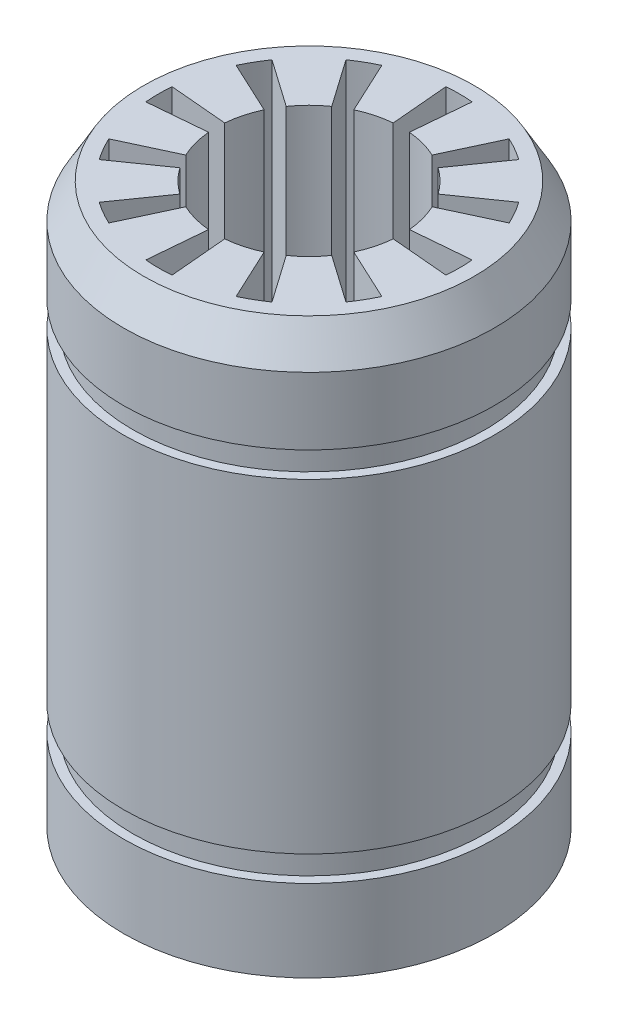
SolidWorks part; units mm, degrees
ref_plane "Front Plane" through (0, 0, 0) normal (0, 0, 1) x (1, 0, 0)
ref_plane "Top Plane" through (0, 0, 0) normal (0, 1, 0) x (1, 0, 0)
ref_plane "Right Plane" through (0, 0, 0) normal (1, 0, 0) x (0, 0, -1)
ref_plane "Plane4" through (0, 0, 0) normal (0, 0, -1) x (-1, 0, 0)
sketch "Sketch1" plane through (0, 0, 0) normal (0, 0, -1) x (-1, 0, 0)
  line L0 (-8, -12.5) -> (0, -12.5)
  line L1 (0, -12.5) -> (0, 12.5)
  line L2 (0, 12.5) -> (-8, 12.5)
  line L3 (-8, 12.5) -> (-8, 8.1)
  line L4 (-8, 8.1) -> (-7.6, 8.1)
  line L5 (-7.6, 8.1) -> (-7.6, 7)
  line L6 (-7.6, 7) -> (-8, 7)
  line L7 (-8, 7) -> (-8, -7)
  line L8 (-8, -7) -> (-7.6, -7)
  line L9 (-7.6, -7) -> (-7.6, -8.1)
  line L10 (-7.6, -8.1) -> (-8, -8.1)
  line L11 (-8, -8.1) -> (-8, -12.5)
  line L12 (0, -12.5) -> (0, 12.5) construction
  dimension "D1" = 0.4
  dimension "D2" = 8
  dimension "D3" = 4.4
  dimension "D4" = 5.5
  dimension "D5" = 19.5
  dimension "D6" = 20.6
  dimension "D7" = 25
revolve "Revolve1" add sketch "Sketch1" angle 360 about L12 reverse direction yes
sketch "Sketch2" plane through (0, -12.5, 0) normal (0, -1, 0) x (1, 0, 0)
  line L0 (-1.6905, 3.6252) -> (-2.747, 5.891)
  line L1 (-3.7282, 5.3245) -> (-2.2943, 3.2766)
  line L2 (-3.2766, 2.2943) -> (-5.3245, 3.7282)
  line L3 (-5.891, 2.747) -> (-3.6252, 1.6905)
  line L4 (-3.9848, 0.3486) -> (-6.4753, 0.5665)
  line L5 (-6.4753, -0.5665) -> (-3.9848, -0.3486)
  line L6 (-3.6252, -1.6905) -> (-5.891, -2.747)
  line L7 (-5.3245, -3.7282) -> (-3.2766, -2.2943)
  line L8 (-2.2943, -3.2766) -> (-3.7282, -5.3245)
  line L9 (-2.747, -5.891) -> (-1.6905, -3.6252)
  line L10 (-0.3486, -3.9848) -> (-0.5665, -6.4753)
  line L11 (0.5665, -6.4753) -> (0.3486, -3.9848)
  line L12 (1.6905, -3.6252) -> (2.747, -5.891)
  line L13 (3.7282, -5.3245) -> (2.2943, -3.2766)
  line L14 (3.2766, -2.2943) -> (5.3245, -3.7282)
  line L15 (5.891, -2.747) -> (3.6252, -1.6905)
  line L16 (3.9848, -0.3486) -> (6.4753, -0.5665)
  line L17 (6.4753, 0.5665) -> (3.9848, 0.3486)
  line L18 (3.6252, 1.6905) -> (5.891, 2.747)
  line L19 (5.3245, 3.7282) -> (3.2766, 2.2943)
  line L20 (2.2943, 3.2766) -> (3.7282, 5.3245)
  line L21 (2.747, 5.891) -> (1.6905, 3.6252)
  line L22 (0.3486, 3.9848) -> (0.5665, 6.4753)
  line L23 (-0.5665, 6.4753) -> (-0.3486, 3.9848)
  arc A0 (-0.3486, 3.9848) -> (-1.6905, 3.6252) centre (0, 0) ccw
  arc A1 (-2.747, 5.891) -> (-3.7282, 5.3245) centre (0, 0) ccw
  arc A2 (-2.2943, 3.2766) -> (-3.2766, 2.2943) centre (0, 0) ccw
  arc A3 (-5.3245, 3.7282) -> (-5.891, 2.747) centre (0, 0) ccw
  arc A4 (-3.6252, 1.6905) -> (-3.9848, 0.3486) centre (0, 0) ccw
  arc A5 (-6.4753, 0.5665) -> (-6.4753, -0.5665) centre (0, 0) ccw
  arc A6 (-3.9848, -0.3486) -> (-3.6252, -1.6905) centre (0, 0) ccw
  arc A7 (-5.891, -2.747) -> (-5.3245, -3.7282) centre (0, 0) ccw
  arc A8 (-3.2766, -2.2943) -> (-2.2943, -3.2766) centre (0, 0) ccw
  arc A9 (-3.7282, -5.3245) -> (-2.747, -5.891) centre (0, 0) ccw
  arc A10 (-1.6905, -3.6252) -> (-0.3486, -3.9848) centre (0, 0) ccw
  arc A11 (-0.5665, -6.4753) -> (0.5665, -6.4753) centre (0, 0) ccw
  arc A12 (0.3486, -3.9848) -> (1.6905, -3.6252) centre (0, 0) ccw
  arc A13 (2.747, -5.891) -> (3.7282, -5.3245) centre (0, 0) ccw
  arc A14 (2.2943, -3.2766) -> (3.2766, -2.2943) centre (0, 0) ccw
  arc A15 (5.3245, -3.7282) -> (5.891, -2.747) centre (0, 0) ccw
  arc A16 (3.6252, -1.6905) -> (3.9848, -0.3486) centre (0, 0) ccw
  arc A17 (6.4753, -0.5665) -> (6.4753, 0.5665) centre (0, 0) ccw
  arc A18 (3.9848, 0.3486) -> (3.6252, 1.6905) centre (0, 0) ccw
  arc A19 (5.891, 2.747) -> (5.3245, 3.7282) centre (0, 0) ccw
  arc A20 (3.2766, 2.2943) -> (2.2943, 3.2766) centre (0, 0) ccw
  arc A21 (3.7282, 5.3245) -> (2.747, 5.891) centre (0, 0) ccw
  arc A22 (1.6905, 3.6252) -> (0.3486, 3.9848) centre (0, 0) ccw
  arc A23 (0.5665, 6.4753) -> (-0.5665, 6.4753) centre (0, 0) ccw
  circle A24 centre (0, 0) radius 8 construction
  dimension "D1" = 4
  dimension "D2" = 6.5
  dimension "D3" = 4
  dimension "D4" = 6.5
  dimension "D5" = 4
  dimension "D6" = 6.5
  dimension "D7" = 4
  dimension "D8" = 6.5
  dimension "D9" = 4
  dimension "D10" = 6.5
  dimension "D11" = 4
  dimension "D12" = 6.5
  dimension "D13" = 4
  dimension "D14" = 6.5
  dimension "D15" = 4
  dimension "D16" = 6.5
  dimension "D17" = 4
  dimension "D18" = 6.5
  dimension "D19" = 4
  dimension "D20" = 6.5
  dimension "D21" = 4
  dimension "D22" = 6.5
  dimension "D23" = 4
  dimension "D24" = 6.5
  dimension "D25" = 0.3486
  dimension "D26" = 0.5665
  dimension "D27" = 1.6905
  dimension "D28" = 3.9848
  dimension "D29" = 0.3486
extrude "Cut-Extrude1" cut sketch "Sketch2" against normal through all
chamfer "Chamfer1" distance 0.866 angle 60 2 edges at (0, -12.5, 8) (0, 12.5, 8) first distance on face at (0, -12.5, 8) first distance on face at (0, 12.5, 0)
